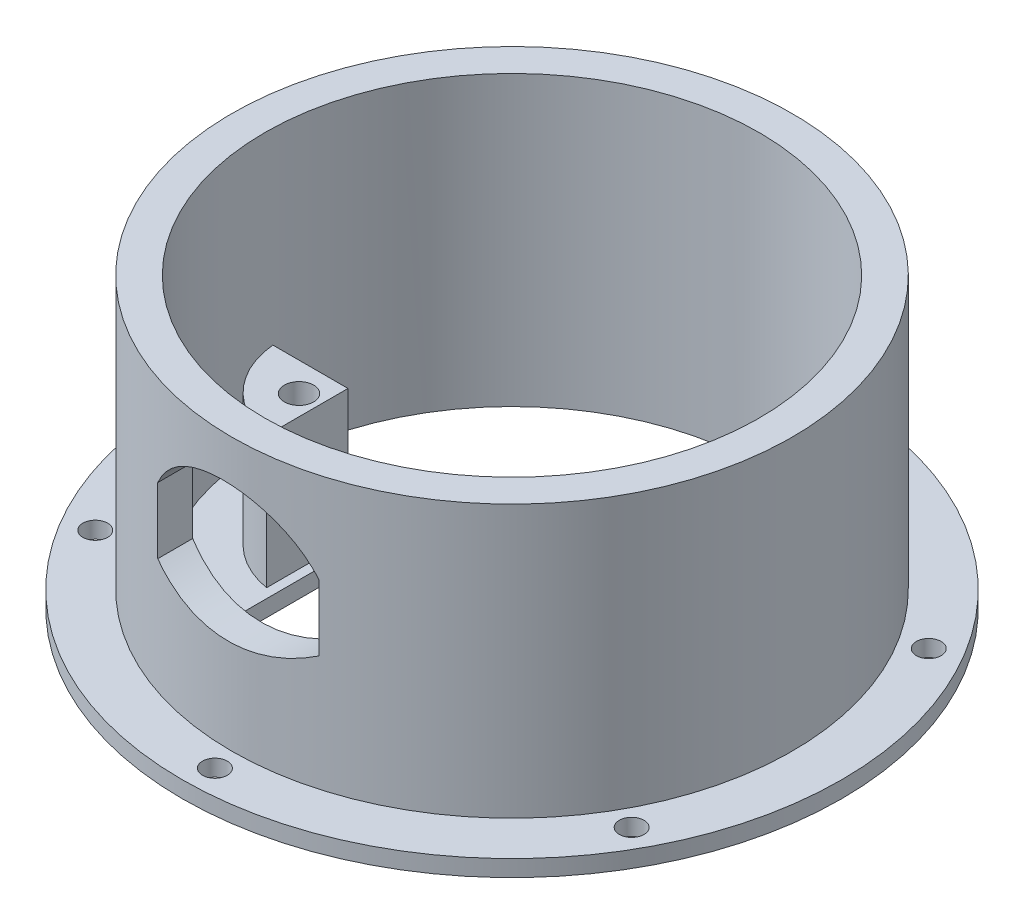
SolidWorks part; units mm, degrees
ref_plane "Front Plane" through (0, 0, 0) normal (0, 0, 1) x (1, 0, 0)
ref_plane "Top Plane" through (0, 0, 0) normal (0, 1, 0) x (1, 0, 0)
ref_plane "Right Plane" through (0, 0, 0) normal (1, 0, 0) x (0, 0, -1)
sketch "Sketch1" plane through (0, 0, 0) normal (0, 1, 0) x (1, 0, 0)
  circle A0 centre (0, 0) radius 40
  circle A1 centre (0, 0) radius 30
  dimension "D1" = 80
  dimension "D2" = 60
extrude "Boss-Extrude1" add sketch "Sketch1" along normal blind 2
sketch "Sketch2" plane through (0, 2, 0) normal (0, 1, 0) x (1, 0, 0)
  circle A0 centre (0, 0) radius 30 construction
  circle A1 centre (0, 0) radius 30
  circle A2 centre (0, 0) radius 34
  dimension "D1" = 4
extrude "Boss-Extrude2" add sketch "Sketch2" along normal blind 33
ref_plane "Plane1" through (0, 15, 0) normal (0, 1, 0) x (1, 0, 0)
sketch "Sketch9" plane through (0, 0, 0) normal (0, 1, 0) x (1, 0, 0)
  line L0 (-29.8657, -2.8351) -> (29.8657, -2.8351)
  line L1 (0, 30) -> (0, -48.3805) construction
  line L2 (-30, 0) -> (59.405, 0) construction
  circle A0 centre (0, 0) radius 30 construction
  arc A1 (29.8657, -2.8351) -> (0, -30) centre (0, 0) cw
  arc A2 (-29.8657, -2.8351) -> (0, -30) centre (0, 0) ccw
extrude "Boss-Extrude3" add sketch "Sketch9" along normal blind 2
sketch "Sketch11" plane through (0, 2, 0) normal (0, 1, 0) x (1, 0, 0)
  line L0 (-24.1735, -4.8351) -> (-15.0625, -4.8351)
  line L1 (-15.0625, -4.8351) -> (-15.0625, -14.7177)
  line L2 (0, 30) -> (0, 39.1404) construction
  line L3 (24.1735, -4.8351) -> (15.0625, -4.8351)
  line L4 (15.0625, -4.8351) -> (15.0625, -14.7177)
  line L5 (-29.8657, -2.8351) -> (29.8657, -2.8351) construction
  arc A0 (-24.1735, -4.8351) -> (-15.0625, -14.7177) centre (-13.1735, -3.8351) ccw
  arc A1 (24.1735, -4.8351) -> (15.0625, -14.7177) centre (13.1735, -3.8351) cw
  dimension "D1" = 2
ref_plane "Plane2" through (0, 0, 35) normal (0, 0, 1) x (1, 0, 0)
sketch "Sketch10" plane through (0, 0, 35) normal (0, 0, 1) x (1, 0, 0)
  line L1 (9.2889, 24.0041) -> (9.2889, 16.0041)
  line L2 (-10.7111, 24.0041) -> (-10.7111, 16.0041)
  arc A0 (9.2889, 16.0041) -> (-10.7111, 16.0041) centre (-0.7111, 33.4299) cw
  arc A1 (-10.7111, 24.0041) -> (9.2889, 24.0041) centre (-0.7111, 18.5894) cw
extrude "Cut-Extrude1" cut sketch "Sketch10" against normal blind 7
extrude "Boss-Extrude4" add sketch "Sketch11" along normal blind 16
sketch "Sketch12" plane through (0, 18, 0) normal (0, 1, 0) x (1, 0, 0)
  line L0 (0, 0) -> (0, 7.1822) construction
  line L1 (0, 30) -> (0, -48.3805) construction
  line L2 (-15.0625, -4.8351) -> (-24.1735, -4.8351) construction
  circle A0 centre (-17.5, -8.3351) radius 1.775
  circle A1 centre (17.5, -8.3351) radius 1.775
  dimension "D1" = 35
  dimension "D2" = 3.5
extrude "Cut-Extrude2" cut sketch "Sketch12" against normal blind 9
sketch "Sketch13" plane through (0, 2, 0) normal (0, 1, 0) x (1, 0, 0)
  line L0 (-13.9184, -20.8807) -> (-13.9184, 1.1193)
  line L1 (-13.9184, 1.1193) -> (14.0816, 1.1193)
  line L2 (14.0816, 1.1193) -> (14.0816, -20.8807)
  arc A0 (14.0816, -20.8807) -> (-13.9184, -20.8807) centre (0.0816, -8.9643) cw
  dimension "D1" = 28
extrude "Cut-Extrude3" cut sketch "Sketch13" against normal blind 10
sketch "Sketch14" plane through (0, 2, 0) normal (0, 1, 0) x (1, 0, 0)
  circle A0 centre (-0.7637, 36.8087) radius 1.5
  circle A1 centre (31.4954, 19.0657) radius 1.5
  circle A2 centre (32.2591, -17.7429) radius 1.5
  circle A3 centre (0.7637, -36.8087) radius 1.5
  circle A4 centre (-31.4954, -19.0657) radius 1.5
  circle A5 centre (-32.2591, 17.7429) radius 1.5
  point P14 (0, 0)
  dimension "D1" = 6
extrude "Cut-Extrude4" cut sketch "Sketch14" against normal up to surface (2 mm away) up to face at (0, 0, 40)
